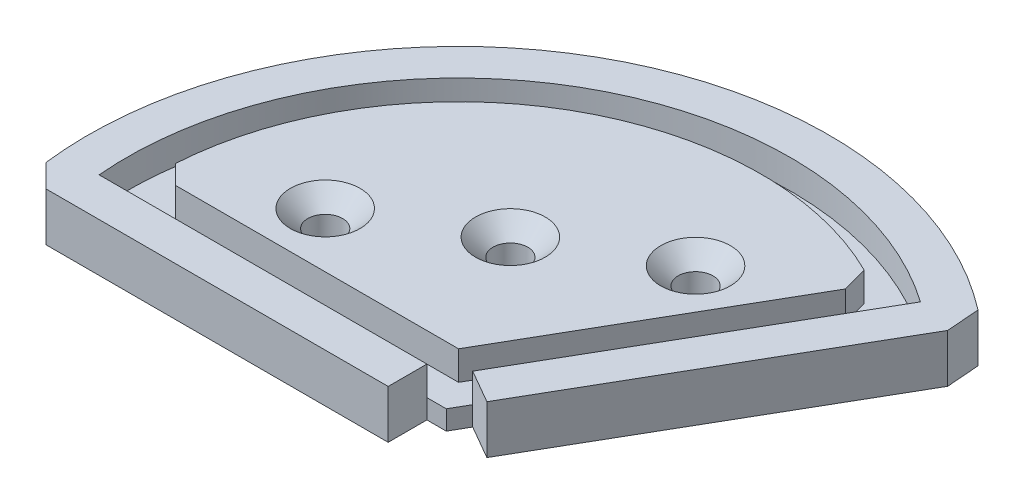
SolidWorks part; units mm, degrees
ref_plane "Front Plane" through (0, 0, 0) normal (0, 0, 1) x (1, 0, 0)
ref_plane "Top Plane" through (0, 0, 0) normal (0, 1, 0) x (1, 0, 0)
ref_plane "Right Plane" through (0, 0, 0) normal (1, 0, 0) x (0, 0, -1)
sketch "Sketch15" plane through (0, 0, 0) normal (0, 1, 0) x (1, 0, 0)
  line L0 (0, 0) -> (-15.625, 0)
  line L1 (0, 0) -> (7.8125, 13.5316)
  arc A0 (7.8125, 13.5316) -> (-15.625, 0) centre (0, 0) ccw
  dimension "D1" = 15.625
  dimension "D2" = 120
extrude "Boss-Extrude8" add sketch "Sketch15" along normal blind 1.5
sketch "Sketch16" plane through (0, 1.5, 0) normal (0, 1, 0) x (1, 0, 0)
  line L2 (2.0207, -3.5) -> (12.4321, 14.533)
  line L3 (-18.802, -3.5) -> (2.0207, -3.5)
  line L4 (0.866, -1.5) -> (9.8286, 14.0237)
  line L5 (-17.0592, -1.5) -> (0.866, -1.5)
  line L6 (0.866, -1.5) -> (9.8286, 14.0237)
  line L7 (-17.0592, -1.5) -> (0.866, -1.5)
  arc A1 (12.4321, 14.533) -> (-18.802, -3.5) centre (0, 0) ccw
  arc A2 (9.8286, 14.0237) -> (-17.0592, -1.5) centre (0, 0) ccw
  arc A3 (9.8286, 14.0237) -> (-17.0592, -1.5) centre (0, 0) ccw
  dimension "D1" = 1.5
  dimension "D2" = 2
extrude "Boss-Extrude9" add sketch "Sketch16" along normal up to surface (1.5 mm away) from surface at -1.5 separate body up to face at (-3.9062, 1.5, -6.7658) starting at face at (-3.9062, 0, -6.7658)
sketch "Sketch17" plane through (0, 0, 0) normal (0, -1, 0) x (1, 0, 0)
  line L2 (12.4321, -14.533) -> (2.0207, 3.5)
  line L3 (2.0207, 3.5) -> (-18.802, 3.5)
  line L4 (12.4321, -14.533) -> (2.0207, 3.5)
  line L5 (2.0207, 3.5) -> (-18.802, 3.5)
  arc A1 (-18.802, 3.5) -> (12.4321, -14.533) centre (0, 0) ccw
  arc A2 (-18.802, 3.5) -> (12.4321, -14.533) centre (0, 0) ccw
  line M4 (7.8125, -13.5316) -> (0, 0)
  line M5 (0, 0) -> (-15.625, 0)
  arc M6 (-15.625, 0) -> (7.8125, -13.5316) centre (0, 0) ccw
  dimension "D1" = 0
extrude "Boss-Extrude10" add sketch "Sketch17" along normal blind 1 contours L5 A2 L4 M4 M6 M5
sketch "Sketch18" plane through (0, 1.5, 0) normal (0, 1, 0) x (1, 0, 0)
  line L4 (-1.1547, 2) -> (5.0067, 12.6718)
  line L5 (-13.4774, 2) -> (-1.1547, 2)
  line L6 (-1.1547, 2) -> (5.0067, 12.6718)
  line L7 (-13.4774, 2) -> (-1.1547, 2)
  arc A2 (5.0067, 12.6718) -> (-13.4774, 2) centre (0, 0) ccw
  arc A3 (5.0067, 12.6718) -> (-13.4774, 2) centre (0, 0) ccw
  dimension "D1" = 2
chamfer "Chamfer2" distance 1 angle 45 2 edges at (7.8125, 0.75, -13.5316) (-15.625, 0.75, 0)
sketch "Sketch19" plane through (0, 1.5, 0) normal (0, 1, 0) x (1, 0, 0)
  line L0 (-0.134, -1.5) -> (-0.134, -3.5)
  line L3 (1.366, -0.634) -> (3.0981, -1.634)
  line L4 (0.866, -1.5) -> (9.8286, 14.0237) construction
  line L5 (2.0207, -3.5) -> (12.4321, 14.533) construction
  line L6 (-17.0592, -1.5) -> (0.866, -1.5) construction
  line L7 (-18.802, -3.5) -> (2.0207, -3.5) construction
  line L8 (-0.134, -3.5) -> (2.0207, -3.5)
  line L9 (2.0207, -3.5) -> (3.0981, -1.634)
  line L10 (-0.134, -1.5) -> (0.866, -1.5)
  line L11 (0.866, -1.5) -> (1.366, -0.634)
  point P13 (0.866, -1.5)
  dimension "D1" = 1
  dimension "D2" = 1
extrude "Cut-Extrude6" cut sketch "Sketch19" against normal through all
chamfer "Chamfer5" distance 1 angle 45 2 edges at (12.4321, 0.25, -14.533) (-18.802, 0.25, 3.5)
sketch "Sketch20" plane through (0, 1.5, 0) normal (0, 1, 0) x (1, 0, 0)
  line L0 (-14.625, 0) -> (7.3125, 12.6656) construction
  line L1 (0, 0) -> (-7.8125, 13.5316) construction
  arc A0 (6.9575, 13.9905) -> (-15.5949, 0.9699) centre (0, 0) ccw construction
  point P10 (-9.7184, 2.8328)
  point P11 (2.4059, 9.8328)
  point P14 (-3.6562, 6.3328)
  dimension "D1" = 7
  dimension "D2" = 7
hole_wizard "CSK for M1.6 Countersunk Flat Head Screw1" positions "Sketch20" profile "Sketch21" countersink size "M1.6" standard "ISO"
sketch "Sketch21" plane through (-3.6562, 1.5, -6.3328) normal (1, 0, 0) x (0, 0, 1)
  line L0 (0, 0) -> (0, 3.0408)
  line L1 (0, 3.0408) -> (0.9, 2.5)
  line L2 (0.9, 2.5) -> (0.9, 0.9)
  line L3 (0.9, 0.9) -> (1.8, 0)
  line L5 (1.8, 0) -> (0, 0)
  line L6 (-0.9, 0.9) -> (-1.8, 0) construction
  line L10 (0, 3.0408) -> (-0.9, 2.5) construction
  line L11 (0, -6.35) -> (0, 107.95) construction
  dimension "Hole Dia." = 1.8
  dimension "Hole Depth" = 2.5
  dimension "Near C'Sink Dia." = 3.6
  dimension "Near C'Sink Angle" = 90
  dimension "Drill Angle" = 118
